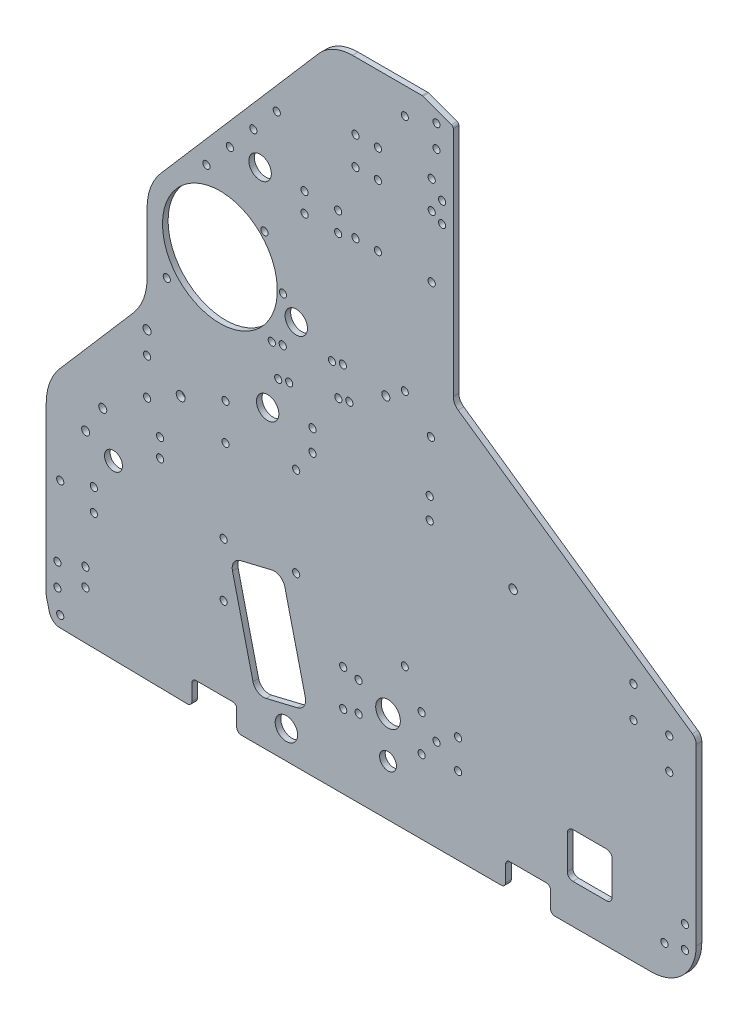
SolidWorks part; units mm, degrees
ref_plane "Front Plane" through (0, 0, 0) normal (0, 0, 1) x (1, 0, 0)
ref_plane "Top Plane" through (0, 0, 0) normal (0, 1, 0) x (1, 0, 0)
ref_plane "Right Plane" through (0, 0, 0) normal (1, 0, 0) x (0, 0, -1)
sketch "Sketch1" plane through (0, 0, 0) normal (0, 0, 1) x (1, 0, 0)
  line L0 (82.55, -20.32) -> (82.55, -6.35)
  line L2 (0, 0) -> (0, 157.48)
  line L4 (368.3, -20.32) -> (368.3, 106.68)
  line L5 (82.55, -6.35) -> (107.95, -6.35)
  line L6 (107.95, -6.35) -> (107.95, -20.32)
  line L7 (107.95, -20.32) -> (260.35, -20.32)
  line L8 (260.35, -20.32) -> (260.35, -6.35)
  line L9 (260.35, -6.35) -> (285.75, -6.35)
  line L10 (285.75, -6.35) -> (285.75, -20.32)
  line L11 (285.75, -20.32) -> (368.3, -20.32)
  line L12 (361.95, 12.7) -> (368.3, 12.7) construction
  line L13 (0, 0) -> (6.35, 0) construction
  line L14 (0.1896, -7.8901) -> (1.7771, -14.2401)
  line L15 (7.8295, -19.0491) -> (82.55, -20.32)
  line L16 (0, 0) -> (0, -6.35)
  line L17 (76.2, 128.905) -> (79.375, 128.905) construction
  line L18 (57.15, 118.5863) -> (101.6, 118.5862) construction
  line L19 (57.15, 118.5863) -> (57.15, 139.2238) construction
  line L20 (101.6, 118.5862) -> (101.6, 139.2237) construction
  line L21 (57.15, 139.2238) -> (101.6, 139.2237) construction
  line L22 (57.15, 118.5863) -> (101.6, 139.2237) construction
  line L23 (101.6, 118.5862) -> (57.15, 139.2238) construction
  line L24 (101.6, 139.2237) -> (125.4682, 147.9111) construction
  line L25 (203.2, 59.805) -> (203.2, 194.805) construction
  line L26 (203.2, 194.805) -> (203.2, 329.805) construction
  line L27 (355.6, 332.105) -> (330.2, 332.105) construction
  line L28 (330.2, 332.105) -> (330.2, 217.805) construction
  line L29 (330.2, 217.805) -> (355.6, 217.805) construction
  line L30 (355.6, 217.805) -> (355.6, 332.105) construction
  line L31 (203.2, 344.805) -> (203.2, 194.805) construction
  line L32 (50.8, 332.105) -> (76.2, 332.105) construction
  line L33 (76.2, 332.105) -> (76.2, 217.805) construction
  line L34 (50.8, 217.805) -> (50.8, 332.105) construction
  line L35 (76.2, 217.805) -> (50.8, 217.805) construction
  line L36 (213.2, 344.805) -> (230.6638, 338.455)
  line L37 (203.2, 344.805) -> (161.925, 344.805)
  line L38 (203.2, 344.805) -> (213.2, 344.805)
  line L39 (348.5362, 344.805) -> (413.4623, 344.805)
  line L40 (348.5362, 344.805) -> (230.6638, 344.805) construction
  line L42 (161.925, 344.805) -> (0, 157.48)
  line L44 (230.6638, 338.455) -> (230.6638, 202.565)
  line L45 (230.6638, 202.565) -> (368.3, 106.68)
  line L46 (213.2, 344.805) -> (-141.0713, 344.805) construction
  line L47 (350.3395, -2.3595) -> (368.3, -20.32) construction
  circle A0 centre (6.35, 0) radius 2.032
  circle A1 centre (6.35, 12.7) radius 2.032
  circle A2 centre (361.95, 0) radius 2.032
  circle A3 centre (361.95, 12.7) radius 2.032
  arc A5 (1.7771, -14.2401) -> (7.8295, -19.0491) centre (7.9375, -12.7) ccw
  circle A6 centre (7.9375, -12.7) radius 2.032
  arc A7 (0, -6.35) -> (0.1896, -7.8901) centre (6.35, -6.35) ccw
  circle A8 centre (38.1, 78.105) radius 5.08
  circle A9 centre (76.2, 128.905) radius 2.54
  circle A10 centre (101.6, 118.5862) radius 2.032
  circle A11 centre (101.6, 139.2237) radius 2.032
  circle A12 centre (57.15, 139.2238) radius 2.032
  circle A13 centre (57.15, 118.5863) radius 2.032
  circle A15 centre (203.2, 59.805) radius 2
  circle A16 centre (203.2, 194.805) radius 2
  circle A17 centre (203.2, 329.805) radius 2
  circle A18 centre (63.5, 313.055) radius 2.032
  circle A20 centre (355.6, 332.105) radius 2.032
  circle A21 centre (330.2, 332.105) radius 2.032
  circle A22 centre (355.6, 217.805) radius 2.032
  circle A23 centre (330.2, 217.805) radius 2.032
  circle A24 centre (50.8, 332.105) radius 2.032
  circle A25 centre (76.2, 332.105) radius 2.032
  circle A26 centre (50.8, 217.805) radius 2.032
  circle A27 centre (76.2, 217.805) radius 2.032
  circle A28 centre (221.1381, 335.28) radius 2
  circle A29 centre (224.3138, 298.831) radius 2.032
  circle A30 centre (353.06, 100.7351) radius 2.032
  circle A31 centre (332.74, 115.9751) radius 2.032
  circle A32 centre (332.74, 98.1951) radius 2.032
  circle A33 centre (353.06, 82.9551) radius 2.032
  circle A34 centre (117.3562, 280.4276) radius 2.032
  circle A35 centre (104.0678, 265.0548) radius 2.032
  circle A36 centre (90.7795, 249.682) radius 2.032
  circle A38 centre (130.6445, 295.8004) radius 2.032
  circle A39 centre (68.326, 182.9237) radius 2.032
  circle A40 centre (224.3138, 287.401) radius 2.032
  circle A41 centre (125.4682, 147.9111) radius 6.35
  circle A42 centre (221.1381, 322.58) radius 2
  circle A43 centre (350.3395, -2.3595) radius 2.032
  point P82 (203.2, 344.805)
  point P90 (368.3, 62.484)
  dimension "D6" = 4.064
  dimension "D10" = 6.35
  dimension "D11" = 4.064
  dimension "D17" = 38.1
  dimension "D27" = 4
  dimension "D31" = 4.064
  dimension "D32" = 41.275
  dimension "D36" = 4.064
  dimension "D47" = 39.624
  dimension "D48" = 4.064
  dimension "D25" = 5.08
  dimension "D26" = 4.064
  dimension "D52" = 4.064
  dimension "D65" = 4.064
  dimension "D69" = 10.16
  dimension "D72" = 12.7
  dimension "D2" = 127
  dimension "D3" = 13.97
  dimension "D4" = 25.4
  dimension "D5" = 152.4
  dimension "D7" = 12.7
  dimension "D8" = 6.35
  dimension "D9" = 20.32
  dimension "D12" = 12.7
  dimension "D13" = 1.5875
  dimension "D14" = 82.55
  dimension "D15" = 368.3
  dimension "D16" = 6.35
  dimension "D18" = 98.425
  dimension "D19" = 38.1
  dimension "D20" = 50.8
  dimension "D21" = 3.175
  dimension "D22" = 270
  dimension "D23" = 20.6375
  dimension "D24" = 44.45
  dimension "D28" = 135
  dimension "D29" = 12.7
  dimension "D30" = 15
  dimension "D33" = 63.5
  dimension "D34" = 27.4638
  dimension "D35" = 12.7
  dimension "D37" = 114.3
  dimension "D38" = 25.4
  dimension "D39" = 12.7
  dimension "D40" = 157.48
  dimension "D41" = 142.24
  dimension "D42" = 365.125
  dimension "D43" = 10
  dimension "D44" = 6.35
  dimension "D45" = 31.75
  dimension "D46" = 3.175
  dimension "D49" = 6.35
  dimension "D50" = 203.2
  dimension "D51" = 15.24
  dimension "D53" = 17.78
  dimension "D54" = 17.78
  dimension "D55" = 20.32
  dimension "D56" = 15.24
  dimension "D57" = 92.202
  dimension "D58" = 8.382
  dimension "D59" = 20.32
  dimension "D60" = 20.32
  dimension "D61" = 8.382
  dimension "D62" = 20.32
  dimension "D63" = 8.382
  dimension "D64" = 8.382
  dimension "D66" = 35.052
  dimension "D67" = 68.326
  dimension "D68" = 11.43
  dimension "D70" = 25.4
  dimension "D71" = 110
  dimension "D73" = 17.9381
  dimension "D74" = 12.7
  dimension "D75" = 45
  dimension "D76" = 25.4
extrude "Boss-Extrude1" add sketch "Sketch1" along normal blind 3.175 contours L16 A7 L14 A5 L15 L2 A0 A1 A6 region at (171.4792, 119.5149, 0)
fillet "Fillet1" radius 2.286 4 edges at (285.75, -6.35, 1.5875) (107.95, -6.35, 1.5875) (260.35, -6.35, 1.5875) (82.55, -6.35, 1.5875)
fillet "Fillet2" radius 6.35 1 edges at (230.6638, 202.565, 1.5875)
sketch "Sketch2" plane through (0, 0, 0) normal (0, 0, -1) x (-1, 0, 0)
  circle A0 centre (-100.5528, 71.086) radius 2.032 construction
  circle A1 centre (-100.5528, 40.606) radius 2.032 construction
  circle A2 centre (-22.225, 18.2025) radius 2.032 construction
  circle A3 centre (-22.225, 8.0425) radius 2.032 construction
  circle A4 centre (-100.5528, 71.086) radius 2.032
  circle A5 centre (-100.5528, 40.606) radius 2.032
  circle A6 centre (-22.225, 18.2025) radius 2.032
  circle A7 centre (-22.225, 8.0425) radius 2.032
extrude "Cut-Extrude1" cut sketch "Sketch2" against normal through all
fillet "Fillet3" radius 1.5875 2 edges at (230.6638, 338.455, 1.5875) (213.2, 344.805, 1.5875)
sketch "Sketch3" plane through (0, 0, 3.175) normal (0, 0, 1) x (1, 0, 0)
  line L0 (132.9524, 63.2646) -> (132.7215, 64.2281) construction
  line L1 (128.3814, 66.8897) -> (110.6828, 62.6472) construction
  line L2 (114.5132, 58.4237) -> (126.8822, 61.3887) construction
  line L3 (108.0212, 58.3071) -> (108.2522, 57.3436) construction
  line L4 (131.2006, 57.703) -> (140.0164, 20.9265) construction
  line L5 (144.0993, 16.7636) -> (132.9524, 63.2646) construction
  line L6 (108.2522, 57.3436) -> (119.3991, 10.8426) construction
  line L7 (121.1509, 16.4042) -> (112.3351, 53.1807) construction
  line L8 (119.3991, 10.8426) -> (119.6301, 9.8791) construction
  line L9 (144.3303, 15.8001) -> (144.0993, 16.7636) construction
  line L10 (137.8383, 15.6835) -> (125.4694, 12.7185) construction
  line L11 (123.9701, 7.2175) -> (141.6687, 11.4601) construction
  line L12 (132.9524, 63.2646) -> (132.7215, 64.2281)
  line L13 (128.3814, 66.8897) -> (110.6828, 62.6472)
  line L14 (114.5132, 58.4237) -> (126.8822, 61.3887)
  line L15 (108.0212, 58.3071) -> (108.2522, 57.3436)
  line L16 (131.2006, 57.703) -> (140.0164, 20.9265)
  line L17 (144.0993, 16.7636) -> (132.9524, 63.2646)
  line L18 (108.2522, 57.3436) -> (119.3991, 10.8426)
  line L19 (121.1509, 16.4042) -> (112.3351, 53.1807)
  line L20 (119.3991, 10.8426) -> (119.6301, 9.8791)
  line L21 (144.3303, 15.8001) -> (144.0993, 16.7636)
  line L22 (137.8383, 15.6835) -> (125.4694, 12.7185)
  line L23 (123.9701, 7.2175) -> (141.6687, 11.4601)
  line L24 (127.7894, 69.3598) -> (110.0908, 65.1172)
  line L25 (105.5512, 57.715) -> (105.7822, 56.7515)
  line L26 (105.7822, 56.7515) -> (116.9291, 10.2505)
  line L27 (116.9291, 10.2505) -> (117.16, 9.287)
  line L28 (124.5622, 4.7475) -> (142.2608, 8.99)
  line L29 (146.8003, 16.3922) -> (146.5694, 17.3557)
  line L30 (146.5694, 17.3557) -> (135.4225, 63.8567)
  line L31 (135.4225, 63.8567) -> (135.1915, 64.8202)
  line L32 (14.605, -0.1369) -> (103.7278, 32.3011) construction
  line L33 (14.605, -0.1369) -> (103.7278, 32.3011)
  line L34 (0, -6.35) -> (0, 157.48) construction
  line L35 (-39.6666, 74.7152) -> (103.7278, 126.9065) construction
  line L36 (26.9875, 46.9531) -> (26.9875, 59.6531) construction
  line L37 (107.95, -20.32) -> (260.35, -20.32) construction
  line L38 (64.5259, 92.5258) -> (64.5259, 102.9405) construction
  line L39 (131.6538, 14.201) -> (136.0946, -4.3242) construction
  arc A0 (132.7215, 64.2281) -> (128.6308, 66.9403) centre (129.2206, 63.3889) ccw construction
  arc A1 (110.6828, 62.6472) -> (110.4377, 62.5791) centre (111.522, 59.1463) ccw construction
  arc A2 (128.6308, 66.9403) -> (128.3814, 66.8897) centre (129.2206, 63.3889) ccw construction
  arc A3 (110.4377, 62.5791) -> (108.0212, 58.3071) centre (111.522, 59.1463) ccw construction
  arc A4 (119.6301, 9.8791) -> (123.7207, 7.1669) centre (123.1309, 10.7183) ccw construction
  arc A5 (141.9139, 11.5281) -> (144.3303, 15.8001) centre (140.8295, 14.9609) ccw construction
  arc A6 (141.6687, 11.4601) -> (141.9139, 11.5281) centre (140.8295, 14.9609) ccw construction
  arc A7 (123.7207, 7.1669) -> (123.9701, 7.2175) centre (123.1309, 10.7183) ccw construction
  arc A8 (132.7215, 64.2281) -> (128.6308, 66.9403) centre (129.2206, 63.3889) ccw
  arc A9 (110.6828, 62.6472) -> (110.4377, 62.5791) centre (111.522, 59.1463) ccw
  arc A10 (128.6308, 66.9403) -> (128.3814, 66.8897) centre (129.2206, 63.3889) ccw
  arc A11 (110.4377, 62.5791) -> (108.0212, 58.3071) centre (111.522, 59.1463) ccw
  arc A12 (119.6301, 9.8791) -> (123.7207, 7.1669) centre (123.1309, 10.7183) ccw
  arc A13 (141.9139, 11.5281) -> (144.3303, 15.8001) centre (140.8295, 14.9609) ccw
  arc A14 (141.6687, 11.4601) -> (141.9139, 11.5281) centre (140.8295, 14.9609) ccw
  arc A15 (123.7207, 7.1669) -> (123.9701, 7.2175) centre (123.1309, 10.7183) ccw
  arc A16 (110.0908, 65.1172) -> (109.6726, 65.0012) centre (111.522, 59.1463) ccw
  arc A17 (109.6726, 65.0012) -> (105.5512, 57.715) centre (111.522, 59.1463) ccw
  arc A18 (117.16, 9.287) -> (124.1369, 4.6613) centre (123.1309, 10.7183) ccw
  arc A19 (124.1369, 4.6613) -> (124.5622, 4.7475) centre (123.1309, 10.7183) ccw
  arc A20 (142.2608, 8.99) -> (142.6789, 9.1061) centre (140.8295, 14.9609) ccw
  arc A21 (142.6789, 9.1061) -> (146.8003, 16.3922) centre (140.8295, 14.9609) ccw
  arc A22 (135.1915, 64.8202) -> (128.2147, 69.446) centre (129.2206, 63.3889) ccw
  arc A23 (128.2147, 69.446) -> (127.7894, 69.3598) centre (129.2206, 63.3889) ccw
  circle A24 centre (136.0946, -4.3242) radius 6.35
  circle A26 centre (134.1438, 208.2281) radius 2.032 construction
  circle A33 centre (26.9875, 46.9531) radius 2.032
  circle A34 centre (26.9875, 59.6531) radius 2.032
  circle A35 centre (7.9375, 53.3031) radius 2.032
  circle A37 centre (32.0306, 100.8109) radius 32.385 construction
  circle A38 centre (32.0306, 100.8109) radius 2.286
  circle A39 centre (123.682, 233.4851) radius 2.032 construction
  circle A40 centre (64.5259, 102.9405) radius 2.032
  circle A41 centre (64.5259, 92.5258) radius 2.032
  circle A42 centre (134.1438, 208.2281) radius 2.032
  circle A43 centre (123.682, 233.4851) radius 2.032
  ellipse E0 centre (124.5974, 48.8487) end of major axis (128.5376, 61.3578) minor radius 6 (131.2006, 57.703) -> (126.8822, 61.3887) ccw construction
  ellipse E1 centre (122.2349, 48.2824) end of major axis (113.0518, 57.6456) minor radius 6 (114.5132, 58.4237) -> (112.3351, 53.1807) ccw construction
  ellipse E2 centre (127.7541, 25.2585) end of major axis (131.6942, 37.7675) minor radius 6 (121.1509, 16.4042) -> (125.4694, 12.7185) ccw construction
  ellipse E3 centre (130.1166, 25.8248) end of major axis (139.2998, 16.4616) minor radius 6 (137.8383, 15.6835) -> (140.0164, 20.9265) ccw construction
  ellipse E4 centre (124.5974, 48.8487) end of major axis (128.5376, 61.3578) minor radius 6 (131.2006, 57.703) -> (126.8822, 61.3887) ccw
  ellipse E5 centre (122.2349, 48.2824) end of major axis (131.4181, 38.9192) minor radius 6 (114.5132, 58.4237) -> (112.3351, 53.1807) ccw
  ellipse E6 centre (127.7541, 25.2585) end of major axis (123.8139, 12.7495) minor radius 6 (121.1509, 16.4042) -> (125.4694, 12.7185) ccw
  ellipse E7 centre (130.1166, 25.8248) end of major axis (139.2998, 16.4616) minor radius 6 (137.8383, 15.6835) -> (140.0164, 20.9265) ccw
  point P93 (26.9875, 53.3031)
  point P115 (32.0306, 100.8109)
  dimension "D3" = 64.77
  dimension "D4" = 4.572
  dimension "D8" = 4.064
  dimension "D13" = 12.7
  dimension "D2" = 88.9
  dimension "D5" = 7.9375
  dimension "D6" = 19.05
  dimension "D7" = 73.6231
  dimension "D9" = 12.7
  dimension "D10" = 10.4147
  dimension "D11" = 37.5384
  dimension "D12" = 45.5727
  dimension "D14" = 19.05
  dimension "D1" = 2.54
extrude "Cut-Extrude2" cut sketch "Sketch3" against normal through all contours A22 A23 L24 A16 A17 L25 L26 L27 A18 A19 L28 A20 A21 L29 L30 L31 A15 A12 L20 L18 L15 A11 A9 L13 A10 A8 L12 L17 L21 A13 A14 L23 | A12 A15 L23 A14 A13 L21 L17 L12 A8 A10 L13 A9 A11 L15 L18 L20 E7 L22 E6 L19 E5 L14 E4 L16 | L22 E7 L16 E4 L14 E5 L19 E6 | A38 | A41 | A40 | A35 | A34 | A33 | A43 | A42 | A24 region at (137.844, 39.8506, 3.175) region at (126.1758, 37.0536, 3.175) region at (128.1544, 68.6507, 3.175) region at (32.0306, 100.8109, 3.175) region at (64.5259, 102.9405, 3.175) region at (64.5259, 92.5258, 3.175)
sketch "Sketch4" plane through (0, 0, 3.175) normal (0, 0, 1) x (1, 0, 0)
  line L0 (57.15, 139.2238) -> (101.6, 139.2237) construction
  line L1 (168.275, 21.4312) -> (212.725, 21.4312) construction
  line L2 (168.275, 21.4312) -> (168.275, 42.0687) construction
  line L3 (168.275, 42.0687) -> (212.725, 42.0687) construction
  line L4 (212.725, 21.4312) -> (212.725, 42.0687) construction
  line L5 (168.275, 21.4312) -> (212.725, 42.0687) construction
  line L6 (168.275, 42.0687) -> (212.725, 21.4312) construction
  line L7 (57.15, 118.5863) -> (57.15, 139.2238) construction
  line L8 (107.95, -20.32) -> (260.35, -20.32) construction
  line L9 (193.675, 31.75) -> (177.005, 31.75) construction
  line L10 (190.5, 31.75) -> (193.675, 31.75) construction
  line L11 (6.35, 12.7) -> (361.95, 12.7) construction
  line L12 (107.95, -6.35) -> (107.95, -20.32) construction
  line L13 (193.675, 31.75) -> (220.6625, 31.75) construction
  line L14 (177.005, 23.4569) -> (177.005, 40.0431) construction
  line L15 (213.2, 44.805) -> (193.2, 44.805) construction
  line L16 (213.2, 44.805) -> (213.2, 344.805) construction
  line L17 (213.2, 344.805) -> (193.2, 344.805) construction
  line L18 (193.2, 44.805) -> (193.2, 344.805) construction
  line L19 (213.2, 44.805) -> (193.2, 344.805) construction
  line L20 (213.2, 344.805) -> (193.2, 44.805) construction
  line L21 (226.1381, 335.28) -> (226.1381, 31.75) construction
  line L22 (237.33, 40.0431) -> (233.3612, 40.0431) construction
  line L23 (237.33, 23.4569) -> (233.3612, 23.4569) construction
  circle A0 centre (168.275, 42.0687) radius 2.032
  circle A1 centre (212.725, 42.0687) radius 2.032
  circle A2 centre (212.725, 21.4312) radius 2.032
  circle A3 centre (168.275, 21.4312) radius 2.032
  circle A4 centre (193.675, 31.75) radius 6.985
  circle A7 centre (220.6625, 31.75) radius 14.2875 construction
  circle A8 centre (193.675, 31.75) radius 12.7 construction
  circle A9 centre (177.005, 40.0431) radius 2.032
  circle A10 centre (177.005, 23.4569) radius 2.032
  circle A11 centre (237.33, 40.0431) radius 2.032 construction
  circle A12 centre (237.33, 23.4569) radius 2.032 construction
  circle A13 centre (193.675, 8.4667) radius 4.7625
  circle A14 centre (221.1381, 31.75) radius 2.032
  circle A15 centre (221.1381, 31.75) radius 5 construction
  circle A16 centre (221.1381, 335.28) radius 5 construction
  circle A17 centre (233.3612, 23.4569) radius 2.032
  circle A18 centre (233.3612, 40.0431) radius 2.032
  point P0 (190.5, 31.75)
  point P26 (203.2, 194.805)
  point P38 (177.005, 31.75)
  dimension "D1" = 4.064
  dimension "D4" = 13.97
  dimension "D7" = 9.525
  dimension "D10" = 25.4
  dimension "D11" = 28.575
  dimension "D16" = 10
  dimension "D17" = 4.064
  dimension "D18" = 10
  dimension "D2" = 52.07
  dimension "D3" = 3.175
  dimension "D5" = 82.55
  dimension "D6" = 26.9875
  dimension "D8" = 20
  dimension "D9" = 300
  dimension "D12" = 16.67
  dimension "D13" = 16.5862
  dimension "D14" = 60.325
  dimension "D15" = 23.2833
  dimension "D19" = 3.9688
extrude "Cut-Extrude3" cut sketch "Sketch4" against normal through all
sketch "Sketch5" plane through (0, 0, 0) normal (0, 0, -1) x (-1, 0, 0)
  line L0 (-57.15, 223.5947) -> (-57.15, 165.3337)
  line L1 (-161.925, 344.805) -> (-52.7201, 218.4699) construction
  line L2 (-57.15, 165.3337) -> (0, 99.219)
  line L3 (0, -6.35) -> (0, 157.48) construction
  line L4 (-147.864, -30.311) -> (-147.864, -16.0874)
  line L5 (-50.4199, 215.8089) -> (0, 157.48) construction
  line L6 (-57.15, 223.5947) -> (0, 157.48)
  line L7 (0, 157.48) -> (0, 99.219)
  line L8 (-98.425, 208.2281) -> (-141.6756, 197.9719) construction
  circle A0 centre (-98.425, 208.2281) radius 32.5437
  circle A1 centre (-141.6756, 197.9719) radius 6.35
  circle A3 centre (-264.5736, 128.3328) radius 2.39
  dimension "D3" = 65.0875
  dimension "D7" = 12.7
  dimension "D8" = 4.78
  dimension "D1" = 38.1
  dimension "D2" = 57.15
  dimension "D4" = 41.275
  dimension "D5" = 41.275
  dimension "D9" = 22.2382
  dimension "D10" = 117.7733
  dimension "D11" = 11.6447
  dimension "D12" = 123.5853
  dimension "D14" = 62.5
  dimension "D13" = 44.45
extrude "Cut-Extrude5" cut sketch "Sketch5" against normal through all contours A0 | L7 L6 L0 L2 | A3 | A1 region at (28.575, 161.4068, 0) region at (98.425, 208.2281, 0) region at (264.5736, 128.3328, 0)
fillet "Fillet4" radius 31.75 3 edges at (0, 99.219, 1.5875) (57.15, 165.3337, 1.5875) (57.15, 223.5947, 1.5875)
sketch "Sketch6" plane through (0, 0, 3.175) normal (0, 0, 1) x (1, 0, 0)
  line L0 (285.75, -20.32) -> (368.3, -20.32) construction
  line L1 (298.45, 27.305) -> (317.5, 27.305)
  line L2 (295.275, 24.13) -> (295.275, 5.08)
  line L3 (298.45, 1.905) -> (317.5, 1.905)
  line L4 (320.675, 24.13) -> (320.675, 5.08)
  line L5 (295.275, 27.305) -> (320.675, 1.905) construction
  line L6 (295.275, 1.905) -> (320.675, 27.305) construction
  line L7 (368.3, -20.32) -> (368.3, 106.68) construction
  arc A0 (295.275, 5.08) -> (298.45, 1.905) centre (298.45, 5.08) ccw
  arc A1 (317.5, 1.905) -> (320.675, 5.08) centre (317.5, 5.08) ccw
  arc A2 (317.5, 27.305) -> (320.675, 24.13) centre (317.5, 24.13) cw
  arc A3 (298.45, 27.305) -> (295.275, 24.13) centre (298.45, 24.13) ccw
  point P0 (307.975, 14.605)
  dimension "D2" = 3.175
  dimension "D1" = 25.4
  dimension "D3" = 22.225
  dimension "D4" = 47.625
extrude "Cut-Extrude6" cut sketch "Sketch6" against normal through all
fillet "Fillet5" radius 25.4 1 edges at (161.925, 344.805, 1.5875)
sketch "Sketch8" plane through (0, 0, 0) normal (0, 0, -1) x (-1, 0, 0)
  line L0 (-230.6638, 337.343) -> (-230.6638, 205.8802) construction
  line L1 (-230.6638, 255.905) -> (-175.26, 255.905) construction
  line L2 (-175.26, 255.905) -> (-175.26, 306.705) construction
  line L3 (-175.26, 306.705) -> (-230.6638, 306.705) construction
  line L4 (-173.5432, 344.805) -> (-212.9203, 344.805) construction
  line L7 (-107.95, -20.32) -> (-260.35, -20.32) construction
  circle A0 centre (-218.44, 290.83) radius 3.9687
  circle A1 centre (-218.44, 290.83) radius 2.032
  circle A2 centre (218.44, 265.7972) radius 3.9687
  circle A3 centre (218.44, 265.7972) radius 2.032
  circle A4 centre (-205.74, 290.83) radius 3.9687
  circle A5 centre (-205.74, 290.83) radius 2.032
  circle A6 centre (-187.96, 290.83) radius 3.9687
  circle A7 centre (-187.96, 290.83) radius 2.032
  circle A8 centre (-187.96, 306.705) radius 2.032
  circle A9 centre (-175.26, 290.83) radius 3.9687
  circle A10 centre (-175.26, 290.83) radius 2.032
  circle A11 centre (-205.74, 306.705) radius 2.032
  circle A13 centre (-205.74, 255.905) radius 2.032
  circle A14 centre (-187.96, 255.905) radius 2.032
  circle A16 centre (-218.44, 306.705) radius 2.032
  circle A17 centre (-175.26, 306.705) radius 2.032
  circle A18 centre (-175.26, 255.905) radius 2.032
  circle A19 centre (-218.44, 255.905) radius 2.032
  circle A20 centre (-218.44, 306.705) radius 3.9687
  circle A21 centre (-205.74, 306.705) radius 3.9687
  circle A22 centre (-175.26, 306.705) radius 3.9687
  circle A23 centre (-218.44, 255.905) radius 3.9687
  circle A24 centre (-205.74, 255.905) radius 3.9687
  circle A25 centre (-187.96, 255.905) radius 3.9687
  circle A26 centre (-175.26, 255.905) radius 3.9687
  circle A27 centre (-187.96, 306.705) radius 3.9687
  dimension "D1" = 7.9375
  dimension "D7" = 4.064
  dimension "D13" = 12.2237
  dimension "D2" = 12.2237
  dimension "D3" = 12.7
  dimension "D4" = 17.78
  dimension "D5" = 12.7
  dimension "D6" = 88.9
  dimension "D8" = 38.1
  dimension "D9" = 17.78
  dimension "D10" = 12.7
  dimension "D11" = 55.4037
  dimension "D12" = 12.7
  dimension "D14" = 311.15
extrude "Cut-Extrude7" cut sketch "Sketch8" against normal through all contours A16 | A17 | A18 | A19 | A8 | A14 | A1 | A7 | A10 region at (218.44, 306.705, 0) region at (175.26, 306.705, 0) region at (175.26, 255.905, 0) region at (218.44, 255.905, 0)
sketch "Sketch10" plane through (0, 0, 3.175) normal (0, 0, 1) x (1, 0, 0)
  circle A4 centre (141.6425, 74.6844) radius 2.032 construction
  circle A5 centre (141.6425, 125.4844) radius 2.032 construction
  circle A6 centre (141.6425, 74.6844) radius 2.032
  circle A7 centre (141.6425, 125.4844) radius 2.032
extrude "Cut-Extrude8" cut sketch "Sketch10" against normal through all
sketch "Sketch11" plane through (0, 0, 3.175) normal (0, 0, 1) x (1, 0, 0)
  ellipse E4 centre (150.8814, 138.43) end of major axis (150.8814, 140.462) minor radius 2.032
  ellipse E5 centre (150.8814, 150.495) end of major axis (150.8814, 152.527) minor radius 2.032
  ellipse E6 centre (217.3024, 150.495) end of major axis (217.3024, 152.527) minor radius 2.032
  ellipse E7 centre (217.3024, 138.43) end of major axis (217.3024, 140.462) minor radius 2.032
extrude "Cut-Extrude9" cut sketch "Sketch11" against normal through all
sketch "Sketch12" plane through (0, 0, 0) normal (0, 0, -1) x (-1, 0, 0)
  line L0 (-173.5432, 344.805) -> (-212.9203, 344.805) construction
  circle A0 centre (-165.4175, 264.635) radius 2.032
  circle A1 centre (-203.2, 329.805) radius 2 construction
  circle A2 centre (-165.4175, 253.5225) radius 2.032
  circle A3 centre (-146.3675, 253.5225) radius 2.032
  circle A4 centre (-146.3675, 264.635) radius 2.032
  dimension "D1" = 80.17
  dimension "D2" = 4.064
  dimension "D3" = 37.7825
  dimension "D4" = 11.1125
  dimension "D5" = 19.05
extrude "Cut-Extrude10" cut sketch "Sketch12" against normal through all
sketch "Sketch14" plane through (0, 0, 0) normal (0, 0, -1) x (-1, 0, 0)
  line L0 (-130.6445, 295.8004) -> (-121.1847, 263.6885) construction
  line L1 (-121.1847, 263.6885) -> (-90.7795, 249.682) construction
  line L2 (-154.3272, 336.0154) -> (-64.88, 232.5373) construction
  line L4 (-118.517, 269.4796) -> (-115.3937, 261.0208) construction
  line L5 (-118.517, 269.4796) -> (-126.9758, 266.3562) construction
  line L6 (-126.9758, 266.3562) -> (-123.8524, 257.8974) construction
  line L7 (-115.3937, 261.0208) -> (-123.8524, 257.8974) construction
  line L8 (-118.517, 269.4796) -> (-123.8524, 257.8974) construction
  line L9 (-126.9758, 266.3562) -> (-115.3937, 261.0208) construction
  circle A0 centre (-121.1847, 263.6885) radius 6.376
  dimension "D1" = 22.225
  dimension "D2" = 9.017
extrude "Cut-Extrude11" cut sketch "Sketch14" against normal through all
sketch "Sketch15" plane through (0, 0, 3.175) normal (0, 0, 1) x (1, 0, 0)
  line L0 (38.1, 78.105) -> (35.0376, 98.2034) construction
  line L1 (20.5874, 75.6997) -> (81.7263, 75.6997) construction
  line L2 (57.15, 139.2238) -> (57.15, 151.9238) construction
  line L3 (52.4937, 153.9549) -> (22.3594, 84.8727) construction
  line L4 (56.0505, 156.8833) -> (192.439, 187.1199) construction
  line L5 (52.4937, 153.9549) -> (37.8292, 107.1192) construction
  line L6 (20.5874, 75.6997) -> (38.1, 78.105) construction
  line L7 (35.0376, 98.2034) -> (37.8292, 107.1192) construction
  line L8 (20.5874, 75.6997) -> (22.3594, 84.8727) construction
  line L9 (38.1, 78.105) -> (17.7697, 78.105) construction
  line L10 (17.7697, 78.105) -> (21.6586, 86.5998) construction
  line L11 (21.6586, 86.5998) -> (52.4937, 153.9549) construction
  circle A0 centre (20.5874, 75.6997) radius 2.159 construction
  circle A1 centre (20.5874, 75.6997) radius 2.159 construction
  circle A2 centre (57.15, 139.2238) radius 2.032 construction
  circle A3 centre (57.15, 139.2238) radius 2.032 construction
  circle A4 centre (57.15, 151.9238) radius 2.286
  circle A5 centre (192.439, 187.1199) radius 2.286
  circle A6 centre (57.15, 151.9238) radius 5.08 construction
  circle A7 centre (38.1, 78.105) radius 2.159 construction
  circle A8 centre (38.1, 78.105) radius 2.159
  arc A9 (163.8737, 173.6806) -> (164.5125, 170.7993) centre (165.557, 172.5423) ccw construction
  arc A10 (173.4398, 172.7784) -> (172.801, 175.6597) centre (171.7565, 173.9167) ccw construction
  arc A11 (172.801, 175.6597) -> (173.4398, 172.7784) centre (171.7565, 173.9167) ccw construction
  arc A12 (164.5125, 170.7993) -> (163.8737, 173.6806) centre (165.557, 172.5423) ccw construction
  arc A13 (169.1589, 192.0883) -> (169.7976, 189.2071) centre (168.1143, 190.3453) ccw construction
  arc A14 (169.7976, 189.2071) -> (169.1589, 192.0883) centre (168.1143, 190.3453) ccw construction
  arc A15 (160.2316, 190.1092) -> (160.8704, 187.2279) centre (161.9149, 188.9709) ccw construction
  arc A16 (160.8704, 187.2279) -> (160.2316, 190.1092) centre (161.9149, 188.9709) ccw construction
  arc A17 (129.7766, 166.1214) -> (130.4154, 163.2402) centre (131.4599, 164.9832) ccw construction
  arc A18 (139.3426, 165.2193) -> (138.7039, 168.1005) centre (137.6593, 166.3576) ccw construction
  arc A19 (138.7039, 168.1005) -> (139.3426, 165.2193) centre (137.6593, 166.3576) ccw construction
  arc A20 (130.4154, 163.2402) -> (129.7766, 166.1214) centre (131.4599, 164.9832) ccw construction
  arc A21 (135.7005, 181.6479) -> (135.0617, 184.5292) centre (134.0172, 182.7862) ccw construction
  arc A22 (135.0617, 184.5292) -> (135.7005, 181.6479) centre (134.0172, 182.7862) ccw construction
  arc A23 (126.1345, 182.55) -> (126.7732, 179.6688) centre (127.8177, 181.4118) ccw construction
  arc A24 (126.7732, 179.6688) -> (126.1345, 182.55) centre (127.8177, 181.4118) ccw construction
  arc A25 (163.8737, 173.6806) -> (164.5125, 170.7993) centre (165.557, 172.5423) ccw
  arc A26 (173.4398, 172.7784) -> (172.801, 175.6597) centre (171.7565, 173.9167) ccw
  arc A27 (172.801, 175.6597) -> (173.4398, 172.7784) centre (171.7565, 173.9167) ccw
  arc A28 (164.5125, 170.7993) -> (163.8737, 173.6806) centre (165.557, 172.5423) ccw
  arc A29 (169.1589, 192.0883) -> (169.7976, 189.2071) centre (168.1143, 190.3453) ccw
  arc A30 (169.7976, 189.2071) -> (169.1589, 192.0883) centre (168.1143, 190.3453) ccw
  arc A31 (160.2316, 190.1092) -> (160.8704, 187.2279) centre (161.9149, 188.9709) ccw
  arc A32 (160.8704, 187.2279) -> (160.2316, 190.1092) centre (161.9149, 188.9709) ccw
  arc A33 (129.7766, 166.1214) -> (130.4154, 163.2402) centre (131.4599, 164.9832) ccw
  arc A34 (139.3426, 165.2193) -> (138.7039, 168.1005) centre (137.6593, 166.3576) ccw
  arc A35 (138.7039, 168.1005) -> (139.3426, 165.2193) centre (137.6593, 166.3576) ccw
  arc A36 (130.4154, 163.2402) -> (129.7766, 166.1214) centre (131.4599, 164.9832) ccw
  arc A37 (135.7005, 181.6479) -> (135.0617, 184.5292) centre (134.0172, 182.7862) ccw
  arc A38 (135.0617, 184.5292) -> (135.7005, 181.6479) centre (134.0172, 182.7862) ccw
  arc A39 (126.1345, 182.55) -> (126.7732, 179.6688) centre (127.8177, 181.4118) ccw
  arc A40 (126.7732, 179.6688) -> (126.1345, 182.55) centre (127.8177, 181.4118) ccw
  circle A41 centre (22.3594, 84.8727) radius 2.286 construction
  circle A42 centre (22.3594, 84.8727) radius 2.286
  point P39 (52.4937, 153.9549)
  dimension "D2" = 4.572
  dimension "D6" = 10.16
  dimension "D1" = 12.7
  dimension "D3" = 139.7
  dimension "D4" = 12.5
  dimension "D5" = 74.0778
  dimension "D7" = 49.0778
extrude "Cut-Extrude12" cut sketch "Sketch15" against normal through all
sketch "Sketch16" plane through (0, 0, 3.175) normal (0, 0, 1) x (1, 0, 0)
  circle A0 centre (98.425, 208.2281) radius 34.925 construction
  circle A1 centre (98.425, 208.2281) radius 34.925
  circle A2 centre (98.425, 208.2281) radius 36.195
  dimension "D1" = 1.27
fillet "Fillet7" radius 5.08 1 edges at (368.3, 106.68, 1.5875)
fillet "Fillet8" radius 2.54 4 edges at (82.55, -20.32, 1.5875) (107.95, -20.32, 1.5875) (260.35, -20.32, 1.5875) (285.75, -20.32, 1.5875)
sketch "Sketch17" plane through (0, 0, 3.175) normal (0, 0, 1) x (1, 0, 0)
  line L0 (230.6638, 337.343) -> (230.6638, 205.8802) construction
  line L1 (173.5432, 344.805) -> (212.9203, 344.805) construction
  circle A0 centre (217.9638, 179.705) radius 2.032
  dimension "D1" = 12.7
  dimension "D3" = 4.064
  dimension "D2" = 165.1
extrude "Cut-Extrude13" cut sketch "Sketch17" against normal through all contours A0
fillet "Fillet9" radius 25.4 1 edges at (368.3, -20.32, 1.5875)
equation "\"D7@Sketch15\"=\"D5@Sketch15\"-25mm"
